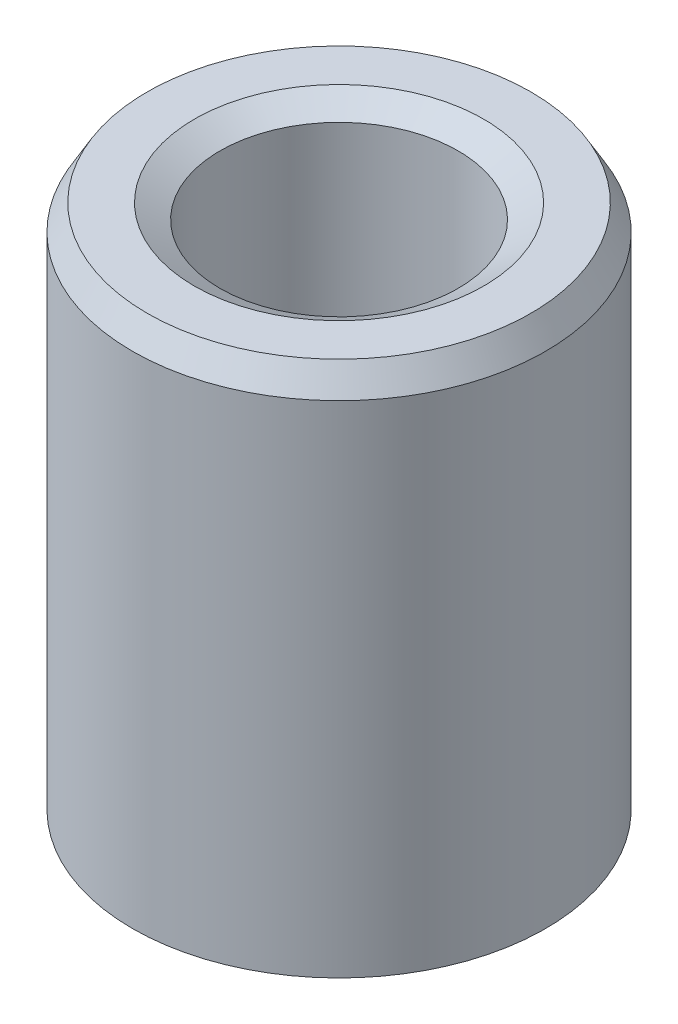
SolidWorks part; units mm, degrees
ref_plane "Front Plane" through (0, 0, 0) normal (0, 0, 1) x (1, 0, 0)
ref_plane "Top Plane" through (0, 0, 0) normal (0, 1, 0) x (1, 0, 0)
ref_plane "Right Plane" through (0, 0, 0) normal (1, 0, 0) x (0, 0, -1)
sketch "Sketch1" plane through (0, 0, 0) normal (0, 1, 0) x (1, 0, 0)
  circle A0 centre (0, 0) radius 27.5
  dimension "SLEEVE_OD" = 55
extrude "Boss-Extrude1" add sketch "Sketch1" along normal blind 71.9178
sketch "Sketch2" plane through (0, 0, 0) normal (0, 1, 0) x (1, 0, 0)
  circle A0 centre (0, 0) radius 15.8613
  dimension "BORE_D" = 31.7225
extrude "Cut-Extrude1" cut sketch "Sketch2" along normal through all
chamfer "Chamfer1" distance 3.3974 angle 30 4 edges at (0, 71.9178, 15.8613) (0, 0, 15.8613) (0, 0, 27.5) (0, 71.9178, 27.5) first distance on face at (0, 71.9178, 15.8613) first distance on face at (0, 0, 15.8613) first distance on face at (0, 71.9178, 27.5)
